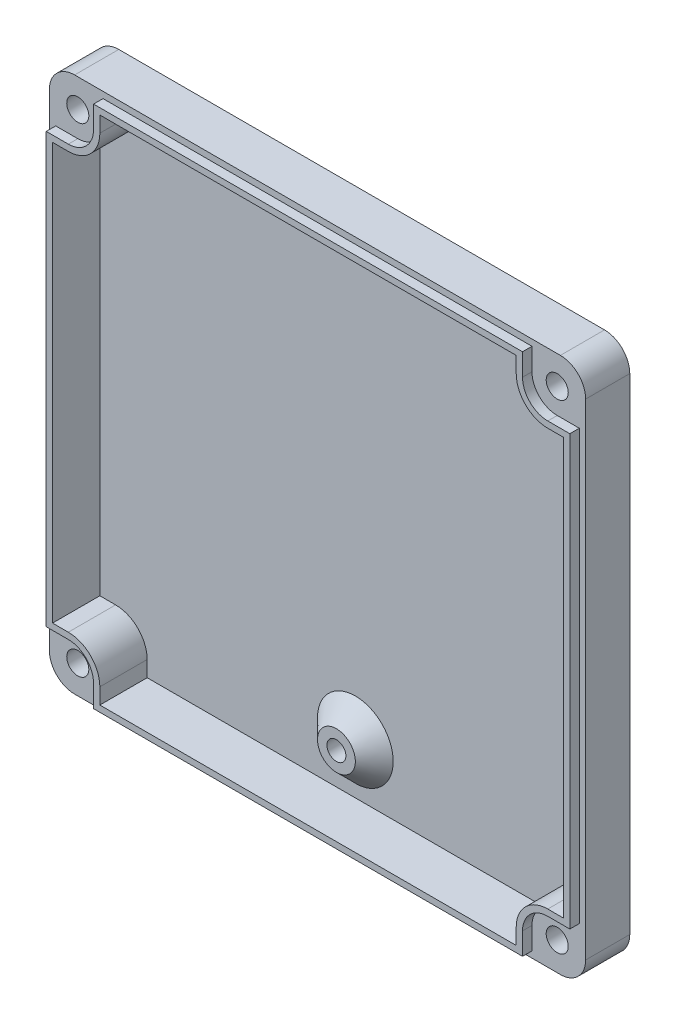
SolidWorks part; units mm, degrees
ref_plane "Front Plane" through (0, 0, 0) normal (0, 0, 1) x (1, 0, 0)
ref_plane "Top Plane" through (0, 0, 0) normal (0, 1, 0) x (1, 0, 0)
ref_plane "Right Plane" through (0, 0, 0) normal (1, 0, 0) x (0, 0, -1)
sketch "Sketch1" plane through (0, 0, 0) normal (0, 0, 1) x (1, 0, 0)
  line L1 (-42.5, -42.5) -> (42.5, -42.5)
  line L2 (-42.5, -42.5) -> (-42.5, 42.5)
  line L3 (-42.5, 42.5) -> (42.5, 42.5)
  line L4 (42.5, -42.5) -> (42.5, 42.5)
  line L5 (-42.5, -42.5) -> (42.5, 42.5) construction
  line L6 (-42.5, 42.5) -> (42.5, -42.5) construction
  point P0 (0, 0)
  dimension "D1" = 85
  dimension "D2" = 85
extrude "Boss-Extrude1" add sketch "Sketch1" along normal blind 7
fillet "Fillet1" radius 4 4 edges at (-42.5, -42.5, 3.5) (42.5, -42.5, 3.5) (42.5, 42.5, 3.5) (-42.5, 42.5, 3.5)
ref_axis "Axis1" through (0, 0, -1.5) along (0, 0, 1)
shell "Shell1" thickness 2 removed face at (0, 0, 7)
sketch "Sketch3" plane through (0, 0, 0) normal (0, 0, 1) x (1, 0, 0)
  line L2 (42.5, -38.5) -> (42.5, 38.5) construction
  line L3 (33.5, 38) -> (33.5, 42.5)
  line L4 (33.5, 42.5) -> (38, 42.5)
  line L5 (42.5, 38) -> (42.5, 33.5)
  line L6 (42.5, 33.5) -> (38, 33.5)
  arc A0 (33.5, 38) -> (38, 33.5) centre (38, 38) ccw
  arc A1 (42.5, 38) -> (38, 42.5) centre (38, 38) ccw
  dimension "D2" = 38
  dimension "D3" = 38
extrude "Boss-Extrude2" add sketch "Sketch3" along normal up to surface (7 mm away) from offset 1 separate body up to face at (0, 0, 7)
pattern_circular "CirPattern5" count 4 over 360 about axis through (0, 0, -1.5) along (0, 0, 1) of bodies 102
combine bodies "Combine1" operation type add bodies to combine 101 106 102 107 108
sketch "Sketch4" plane through (0, 0, 7) normal (0, 0, 1) x (1, 0, 0)
  circle A0 centre (38, 38) radius 1.75
  dimension "D1" = 3.5
extrude "Cut-Extrude1" cut sketch "Sketch4" against normal through all
other "Move Face1" face at (-33.5, 39.25, 4) face at (-35.284, 35.284, 4) face at (-39.25, 33.5, 4) face at (-33.5, -39.25, 4) face at (-39.25, -33.5, 4) face at (-35.284, -35.284, 4) face at (33.5, -39.25, 4) face at (35.284, -35.284, 4) face at (39.25, -33.5, 4) face at (39.25, 33.5, 4) face at (33.5, 39.25, 4) face at (35.284, 35.284, 4) offset 0.5 parameters "D1"=0.5
sketch "Sketch7" plane through (0, 0, 7) normal (0, 0, 1) x (1, 0, 0)
  line L12 (38, -33) -> (40.5, -33)
  line L13 (40.5, -33) -> (40.5, 33)
  line L14 (40.5, 33) -> (38, 33)
  line L15 (33, 38) -> (33, 40.5)
  line L16 (33, 40.5) -> (-33, 40.5)
  line L17 (-33, 40.5) -> (-33, 38)
  line L18 (-38, 33) -> (-40.5, 33)
  line L19 (-40.5, 33) -> (-40.5, -33)
  line L20 (-40.5, -33) -> (-38, -33)
  line L21 (-33, -38) -> (-33, -40.5)
  line L22 (-33, -40.5) -> (33, -40.5)
  line L23 (33, -40.5) -> (33, -38)
  line L24 (38, -33) -> (40.5, -33)
  line L25 (40.5, -33) -> (40.5, 33)
  line L26 (40.5, 33) -> (38, 33)
  line L27 (33, 38) -> (33, 40.5)
  line L28 (33, 40.5) -> (-33, 40.5)
  line L29 (-33, 40.5) -> (-33, 38)
  line L30 (-38, 33) -> (-40.5, 33)
  line L31 (-40.5, 33) -> (-40.5, -33)
  line L32 (-40.5, -33) -> (-38, -33)
  line L33 (-33, -38) -> (-33, -40.5)
  line L34 (-33, -40.5) -> (33, -40.5)
  line L35 (33, -40.5) -> (33, -38)
  arc A4 (33, 38) -> (38, 33) centre (38, 38) ccw
  arc A5 (-38, 33) -> (-33, 38) centre (-38, 38) ccw
  arc A6 (-33, -38) -> (-38, -33) centre (-38, -38) ccw
  arc A7 (38, -33) -> (33, -38) centre (38, -38) ccw
  arc A8 (33, 38) -> (38, 33) centre (38, 38) ccw
  arc A9 (-38, 33) -> (-33, 38) centre (-38, 38) ccw
  arc A10 (-33, -38) -> (-38, -33) centre (-38, -38) ccw
  arc A11 (38, -33) -> (33, -38) centre (38, -38) ccw
  dimension "D1" = 0
extrude "Extrude-Thin1" add sketch "Sketch7" along normal blind 1.5 thin thin type one direction wall 1
chamfer "Chamfer1" [suppressed] distance 3 angle 45
sketch "Sketch13" plane through (0, 0, 1) normal (0, 0, 1) x (1, 0, 0)
  line L0 (33, 40.5) -> (-33, 40.5) construction
  line L1 (-19, 40.5) -> (19, 40.5)
  line L2 (-19, 40.5) -> (-19, 28.5)
  line L3 (-19, 28.5) -> (19, 28.5)
  line L4 (19, 40.5) -> (19, 28.5)
  line L5 (0, 40.5) -> (0, 0) construction
  dimension "D1" = 38
  dimension "D2" = 12
extrude "Boss-Extrude4" [suppressed] add sketch "Sketch13" along normal blind 20
sketch "Sketch14" [suppressed] plane through (0, 0, 22) normal (0, 0, 1) x (1, 0, 0)
  line L0 (-12, 27) -> (-12, 30)
  line L1 (-19, 27) -> (19, 27) construction
  line L2 (-12, 30) -> (-15.5, 30)
  line L3 (-15.5, 30) -> (-15.5, 31.2)
  line L4 (-15.5, 31.2) -> (15.5, 31.2)
  line L5 (15.5, 31.2) -> (15.5, 30)
  line L6 (15.5, 30) -> (13.8, 30)
  line L7 (13.8, 30) -> (13.8, 27)
  line L8 (13.8, 27) -> (-12, 27)
  line L9 (0, 31.2) -> (0, 0) construction
  dimension "D1" = 1.2
  dimension "D2" = 31
  dimension "4" = 3.5
  dimension "D4" = 1.7
  dimension "D5" = 3
extrude "Cut-Extrude4" [suppressed] cut sketch "Sketch14" against normal up to surface (20 mm away)
pattern_circular "CirPattern6" count 4 over 360 about axis through (0, 0, -1.5) along (0, 0, 1) of "Cut-Extrude1"
sketch "Sketch15" plane through (0, 0, 0) normal (0, 0, -1) x (-1, 0, 0)
  circle A0 centre (-38, -38) radius 3.25
  circle A1 centre (38, -38) radius 3.25
  circle A2 centre (38, 38) radius 3.25
  circle A3 centre (-38, 38) radius 3.25
  dimension "D1" = 6.5
extrude "Cut-Extrude5" cut sketch "Sketch15" against normal offset from surface (2 mm away) 5 up to face at (38, -39.75, 7)
sketch "Sketch16" plane through (0, 0, 0) normal (0, 0, -1) x (-1, 0, 0)
  circle A0 centre (-38, -38) radius 1.75 construction
  circle A1 centre (-38, 38) radius 1.75 construction
  circle A2 centre (38, -38) radius 1.75 construction
  circle A3 centre (38, 38) radius 1.75 construction
  circle A4 centre (-38, -38) radius 1.75
  circle A5 centre (-38, 38) radius 1.75
  circle A6 centre (38, -38) radius 1.75
  circle A7 centre (38, 38) radius 1.75
extrude "Extrude-Thin2" add sketch "Sketch16" against normal up to surface (2 mm away) thin up to face at (-41.25, -38, 2) thin type one direction wall 0.5
sketch "Sketch17" plane through (0, 0, 0) normal (0, 0, -1) x (-1, 0, 0)
  line L0 (38.5, -42.5) -> (-38.5, -42.5) construction
  circle A0 centre (0, -32.5) radius 1.5
  dimension "D1" = 3
  dimension "D2" = 10
extrude "Cut-Extrude6" cut sketch "Sketch17" against normal through all
sketch "Sketch18" [suppressed] plane through (0, 0, 22) normal (0, 0, 1) x (1, 0, 0)
  line L1 (-19, 27) -> (-12, 27)
  line L2 (-19, 27) -> (-19, 30)
  line L3 (-19, 30) -> (-12, 30)
  line L4 (-12, 27) -> (-12, 30)
extrude "Cut-Extrude7" [suppressed] cut sketch "Sketch18" against normal offset from surface (15 mm away) 5
sketch "Sketch19" [suppressed] plane through (0, 0, 22) normal (0, 0, 1) x (1, 0, 0)
  line L0 (15.5, 31.2) -> (-15.5, 31.2) construction
  line L1 (14, 31.2) -> (-6, 31.2)
  line L2 (14, 31.2) -> (14, 36.2)
  line L3 (14, 36.2) -> (-6, 36.2)
  line L4 (-6, 31.2) -> (-6, 36.2)
  dimension "D1" = 9.5
  dimension "D2" = 20
  dimension "D3" = 5
extrude "Cut-Extrude8" [suppressed] cut sketch "Sketch19" against normal up to surface (20 mm away)
sketch "Sketch20" [suppressed] plane through (0, 0, 22) normal (0, 0, 1) x (1, 0, 0)
  line L1 (-6, 31.2) -> (-15.5, 31.2) construction
  line L2 (-15.5, 31.2) -> (-15.5, 30) construction
  circle A0 centre (-8.5, 33.7) radius 1.25
  dimension "D1" = 2.5
  dimension "D2" = 2.5
  dimension "D3" = 7
extrude "Cut-Extrude9" [suppressed] cut sketch "Sketch20" against normal blind 5
sketch "Sketch22" plane through (0, 0, 1) normal (0, 0, 1) x (1, 0, 0)
  circle A0 centre (0, -32.5) radius 3
  circle A1 centre (0, -32.5) radius 1.5
  circle A2 centre (0, -32.5) radius 1.5 construction
  dimension "D1" = 6
extrude "Boss-Extrude5" add sketch "Sketch22" along normal blind 3
chamfer "Chamfer2" distance 3 angle 45 1 edges at (-3, -32.5, 1)
